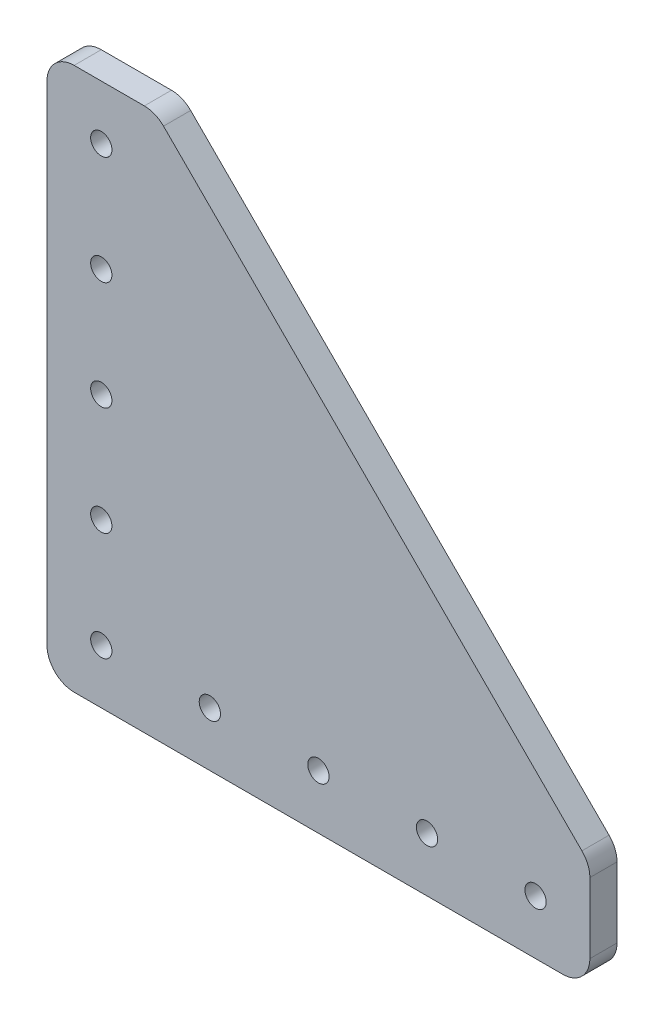
SolidWorks part; units mm, degrees
material "6061-T6 (SS)"
ref_plane "Front Plane" through (0, 0, 0) normal (0, 0, 1) x (1, 0, 0)
ref_plane "Top Plane" through (0, 0, 0) normal (0, 1, 0) x (1, 0, 0)
ref_plane "Right Plane" through (0, 0, 0) normal (1, 0, 0) x (0, 0, -1)
sketch "Sketch1" plane through (0, 0, 0) normal (0, 0, 1) x (1, 0, 0)
  line L0 (0, 0) -> (0, 127)
  line L1 (0, 127) -> (25.4, 127)
  line L2 (25.4, 127) -> (25.4, 25.4)
  line L3 (25.4, 25.4) -> (127, 25.4)
  line L4 (127, 25.4) -> (127, 0)
  line L5 (127, 0) -> (0, 0)
  line L6 (25.4, 127) -> (127, 25.4)
  circle A0 centre (12.7, 12.7) radius 2.4892
  circle A1 centre (38.1, 12.7) radius 2.4892
  circle A2 centre (63.5, 12.7) radius 2.4892
  circle A3 centre (38.1, 38.1) radius 2.4892 construction
  circle A4 centre (63.5, 38.1) radius 2.4892 construction
  circle A5 centre (38.1, 63.5) radius 2.4892 construction
  circle A6 centre (63.5, 63.5) radius 2.4892 construction
  circle A7 centre (38.1, 88.9) radius 2.4892 construction
  circle A8 centre (63.5, 88.9) radius 2.4892 construction
  circle A9 centre (12.7, 38.1) radius 2.4892
  circle A10 centre (12.7, 63.5) radius 2.4892
  circle A11 centre (12.7, 88.9) radius 2.4892
  circle A12 centre (12.7, 114.3) radius 2.4892
  circle A13 centre (38.1, 114.3) radius 2.4892 construction
  circle A14 centre (63.5, 114.3) radius 2.4892 construction
  circle A21 centre (88.9, 12.7) radius 2.4892
  circle A22 centre (114.3, 12.7) radius 2.4892
  circle A24 centre (88.9, 38.1) radius 2.4892 construction
  circle A25 centre (114.3, 38.1) radius 2.4892 construction
  circle A27 centre (88.9, 63.5) radius 2.4892 construction
  circle A28 centre (114.3, 63.5) radius 2.4892 construction
  circle A30 centre (88.9, 88.9) radius 2.4892 construction
  circle A31 centre (114.3, 88.9) radius 2.4892 construction
  circle A33 centre (88.9, 114.3) radius 2.4892 construction
  circle A34 centre (114.3, 114.3) radius 2.4892 construction
  dimension "D2" = 4.9784
  dimension "D1" = 25.4
  dimension "D3" = 12.7
  dimension "D4" = 12.7
  dimension "D7" = 25.4
  dimension "D8" = 25.4
  dimension "D9" = 127
  dimension "D10" = 127
  dimension "D5" = 5
  dimension "D6" = 5
extrude "Boss-Extrude1" add sketch "Sketch1" along normal blind 6.35 contours L5 L4 L3 L2 L1 L0 A22 A21 A12 A11 A10 A9 A2 A1 A0 | L6 L2 L3 region at (1.7961, 63.5, 0) region at (59.2667, 59.2667, 0)
fillet "Fillet1" radius 6.35 5 edges at (0, 0, 3.175) (0, 127, 3.175) (127, 0, 3.175) (25.4, 127, 3.175) (127, 25.4, 3.175)
